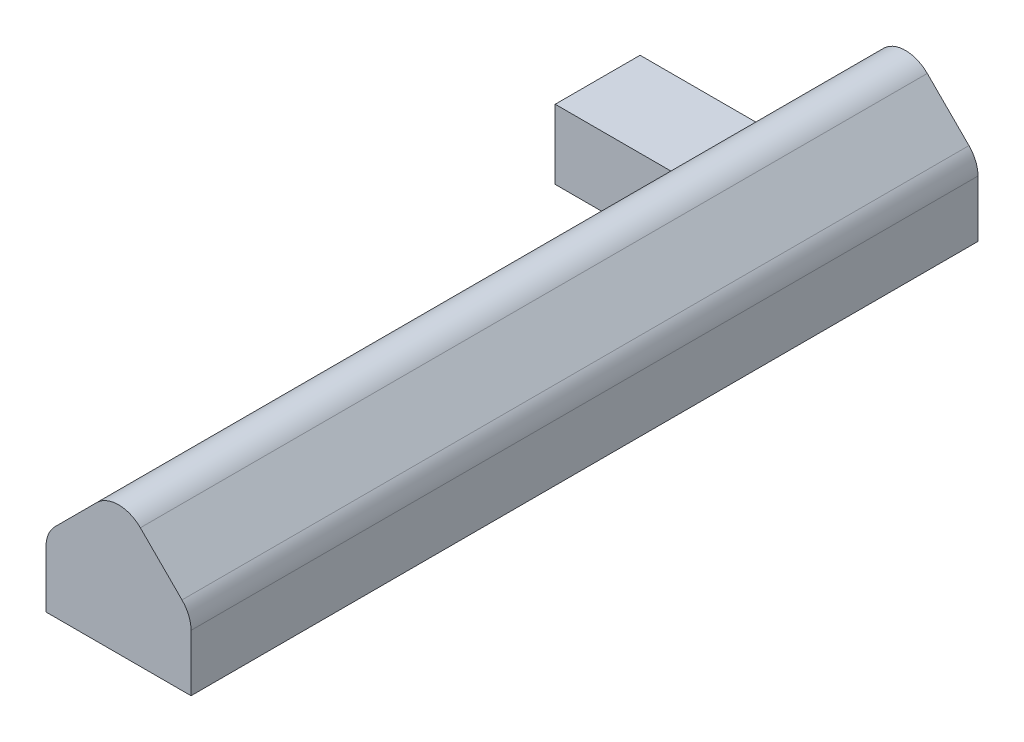
SolidWorks part; units mm, degrees
ref_plane "Płaszczyzna przednia" through (0, 0, 0) normal (0, 0, 1) x (1, 0, 0)
ref_plane "Płaszczyzna górna" through (0, 0, 0) normal (0, 1, 0) x (1, 0, 0)
ref_plane "Płaszczyzna prawa" through (0, 0, 0) normal (1, 0, 0) x (0, 0, -1)
sketch "Szkic1" plane through (0, 0, 0) normal (0, 0, 1) x (1, 0, 0)
  line L0 (0, 0) -> (0, 9.4056) construction
  line L1 (-4.7, 2.25) -> (4.7, 2.25)
  line L2 (-4.7, 2.25) -> (-4.7, -2.25)
  line L3 (-4.7, -2.25) -> (4.7, -2.25)
  line L4 (4.7, 2.25) -> (4.7, -2.25)
  line L5 (-4.7, 2.25) -> (4.7, -2.25) construction
  line L6 (-4.7, -2.25) -> (4.7, 2.25) construction
  line L7 (-4.7, 2.25) -> (0, 6.95)
  line L8 (0, 6.95) -> (4.7, 2.25)
  point P0 (0, 0)
  dimension "D1" = 9.4
  dimension "D2" = 4.5
  dimension "D3" = 45
extrude "Dodanie-wyciągnięcie1" add sketch "Szkic1" along normal blind 51 contours L8 L7 L1 | L4 L1 L2 L3 region at (0, 3.8167, 0) region at (0, 0, 0)
sketch "Szkic2" plane through (0, -2.25, 0) normal (0, -1, 0) x (1, 0, 0)
  line L0 (0, 0) -> (0, 51) construction
  line L1 (-4.7, 0) -> (4.7, 0) construction
  line L2 (-4.7, 51) -> (4.7, 51) construction
  line L3 (4.7, 51) -> (4.7, 0) construction
  line L8 (-10, 32) -> (-10, 37.5)
  line L9 (0, 37.5) -> (-10, 37.5)
  line L10 (0, 32) -> (0, 37.5)
  line L11 (0, 32) -> (-10, 32)
  line L12 (-1.5, 37.5) -> (-1.5, 32)
  line M6 (4.7, 0) -> (4.7, 51)
  line M8 (-4.7, 51) -> (-4.7, 0)
  dimension "D1" = 6.2
  dimension "D2" = 14.7
  dimension "D3" = 5.5
  dimension "D4" = 37.5
extrude "Wytnij-wyciągnięcie1" cut sketch "Szkic2" against normal blind 10 contours M6 | L12 L9 L11 M8 region at (-3.1, -2.25, 34.75)
ref_plane "Płaszczyzna1" through (-22.5, 11.75, 5) normal (0, -1, 0) x (-1, 0, 0)
sketch "Szkic4" plane through (0, -2.25, 0) normal (0, -1, 0) x (1, 0, 0)
  line L0 (0, 0) -> (0, 5) construction
  line L2 (-4.7, 0) -> (4.7, 0) construction
  line L3 (0, 0) -> (0, -7.3747) construction
  line L9 (7.5, -5) -> (-7.5, -5)
  line L10 (7.5, -5) -> (7.5, 5)
  line L11 (7.5, 5) -> (-7.5, 5)
  line L12 (-7.5, -5) -> (-7.5, 5)
  line L13 (7.5, -5) -> (-7.5, 5) construction
  line L14 (7.5, 5) -> (-7.5, -5) construction
  line L15 (13.1781, -10) -> (-13.1781, -10)
  line L16 (13.1781, -10) -> (13.1781, -5)
  line L17 (13.1781, -5) -> (-13.1781, -5)
  line L18 (-13.1781, -10) -> (-13.1781, -5)
  line L19 (13.1781, -10) -> (-13.1781, -5) construction
  line L20 (13.1781, -5) -> (-13.1781, -10) construction
  point P4 (0, 0)
  point P10 (0, -7.5)
  dimension "D1" = 5
  dimension "D2" = 15
  dimension "D3" = 10
  dimension "D4" = 5
fillet "Zaokrąglenie1" radius 2 3 edges at (4.7, 2.25, 25.5) (-4.7, 2.25, 44.25) (0, 6.95, 25.5)
sketch "Szkic5" plane through (0, -2.25, 0) normal (0, -1, 0) x (1, 0, 0)
  line L0 (-4.7, 51) -> (-4.7, 37.5) construction
  line L1 (-4.7, 5) -> (-12.2, 5)
  line L2 (-4.7, 5) -> (-4.7, 10.5)
  line L3 (-4.7, 10.5) -> (-12.2, 10.5)
  line L4 (-12.2, 5) -> (-12.2, 10.5)
  line L5 (-8.45, 10.5) -> (-8.45, 5) construction
  line L6 (-4.7, 7.75) -> (-12.2, 7.75) construction
  line L7 (-4.7, 0) -> (4.7, 0) construction
  line L8 (-4.7, 51) -> (-4.7, 37.5) construction
  point P196 (-8.45, 7.75)
  dimension "D1" = 5.5
  dimension "D2" = 7.5
  dimension "D3" = 5
extrude "Dodanie-wyciągnięcie4" add sketch "Szkic5" against normal up to vertex (4.5 mm away) up to point (-4.7, 2.25, 32)
